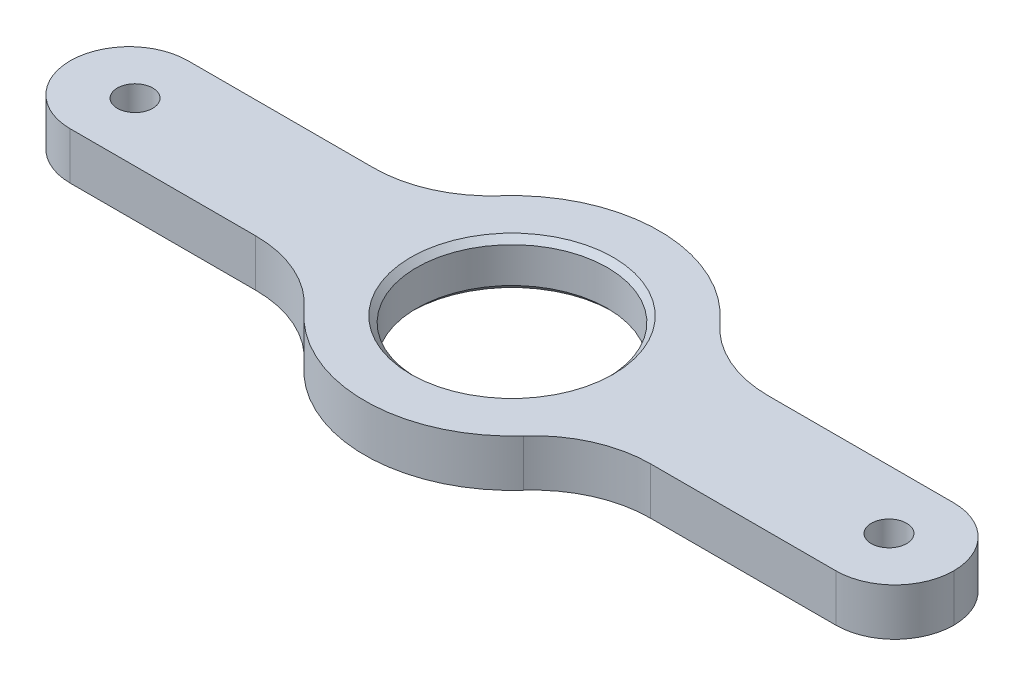
SolidWorks part; units mm, degrees
ref_plane "Front Plane" through (0, 0, 0) normal (0, 0, 1) x (1, 0, 0)
ref_plane "Top Plane" through (0, 0, 0) normal (0, 1, 0) x (1, 0, 0)
ref_plane "Right Plane" through (0, 0, 0) normal (1, 0, 0) x (0, 0, -1)
sketch "Sketch1" plane through (0, 0, 0) normal (0, 1, 0) x (1, 0, 0)
  line L4 (-37.5, -5) -> (37.5, -5)
  line L5 (-37.5, -5) -> (-37.5, 5)
  line L6 (-37.5, 5) -> (37.5, 5)
  line L7 (37.5, -5) -> (37.5, 5)
  line L8 (-37.5, -5) -> (37.5, 5) construction
  line L9 (-37.5, 5) -> (37.5, -5) construction
  point P0 (0, 0)
  point P3 (0, 0)
  dimension "D2" = 75
  dimension "D3" = 10
extrude "Boss-Extrude1" add sketch "Sketch1" along normal blind 4
sketch "Sketch7" plane through (0, 4, 0) normal (0, 1, 0) x (1, 0, 0)
  circle A0 centre (0, 0) radius 12.5
  dimension "D1" = 25
extrude "Boss-Extrude2" add sketch "Sketch7" against normal up to surface (4 mm away) up to face at (0, 0, 0)
sketch "Sketch4" plane through (0, 4, 0) normal (0, 1, 0) x (1, 0, 0)
  circle A0 centre (0, 0) radius 8.1
  dimension "D1" = 16.2
extrude "Cut-Extrude3" cut sketch "Sketch4" against normal through all
fillet "Fillet2" radius 10 4 edges at (11.4564, 2, 5) (-11.4564, 2, 5) (11.4564, 2, -5) (-11.4564, 2, -5)
sketch "Sketch8" plane through (0, 4, 0) normal (0, 1, 0) x (1, 0, 0)
  circle A0 centre (-32, 0) radius 1.5
  point P2 (0, 0)
  point P4 (0, 0)
  dimension "D1" = 3
  dimension "D2" = 32
extrude "Cut-Extrude4" cut sketch "Sketch8" against normal through all
mirror "Mirror2" about plane through (0, 0, 0) normal (1, 0, 0) of "Cut-Extrude4"
fillet "Fillet3" radius 5 4 edges at (-37.5, 2, -5) (-37.5, 2, 5) (37.5, 2, 5) (37.5, 2, -5)
chamfer "Chamfer1" distance 0.5 angle 45 2 edges at (0, 4, 8.1) (0, 0, 8.1)
